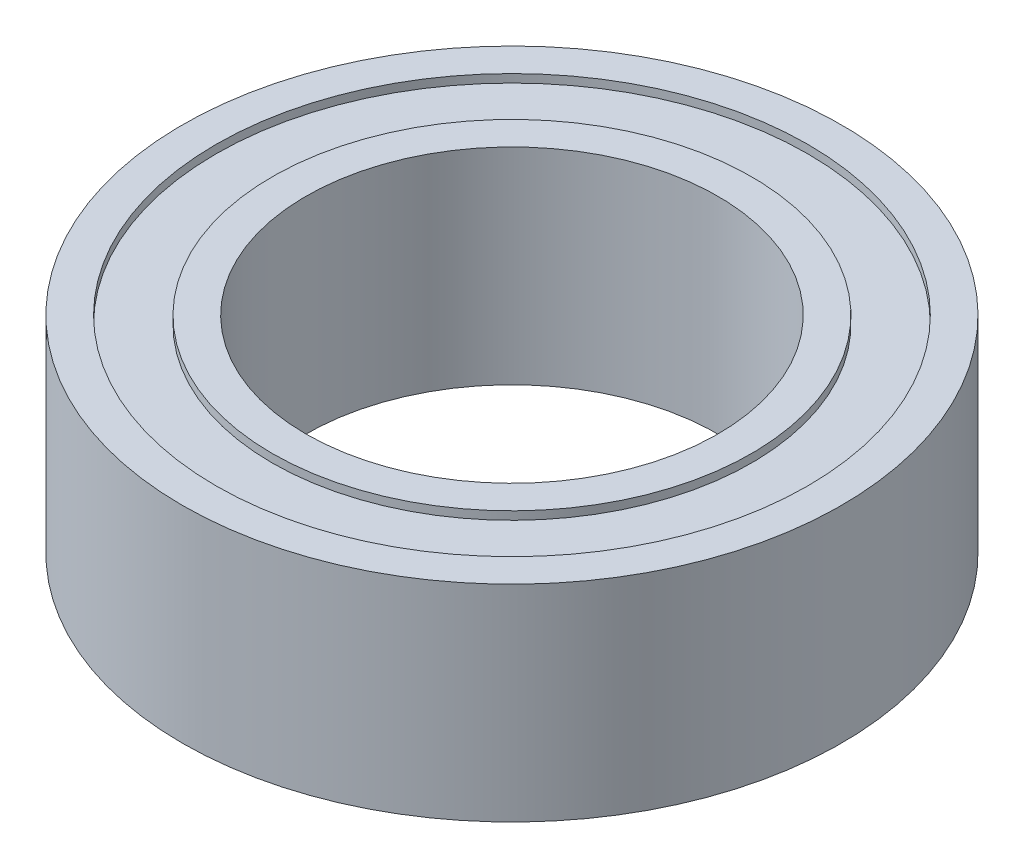
SolidWorks part; units mm, degrees
ref_plane "Front Plane" through (0, 0, 0) normal (0, 0, 1) x (1, 0, 0)
ref_plane "Top Plane" through (0, 0, 0) normal (0, 1, 0) x (1, 0, 0)
ref_plane "Right Plane" through (0, 0, 0) normal (1, 0, 0) x (0, 0, -1)
sketch "Sketch1" plane through (0, 0, 0) normal (0, 1, 0) x (1, 0, 0)
  circle A0 centre (0, 0) radius 4
  circle A1 centre (0, 0) radius 2.5
  dimension "D1" = 8
  dimension "D2" = 5
extrude "Boss-Extrude1" add sketch "Sketch1" along normal blind 1.25
sketch "Sketch2" plane through (0, 1.25, 0) normal (0, 1, 0) x (1, 0, 0)
  line L0 (0, 2.9092) -> (0, 2.5) construction
  line L1 (0, 3.5908) -> (0, 4) construction
  circle A0 centre (0, 0) radius 3.5908
  circle A1 centre (0, 0) radius 2.9092
  circle A2 centre (0, 0) radius 2.5 construction
  circle A3 centre (0, 0) radius 4 construction
  point P12 (0, 3.5908)
extrude "Cut-Extrude1" cut sketch "Sketch2" against normal blind 0.1
mirror "Mirror1" about plane through (0, 0, 0) normal (0, 1, 0) of bodies 104
